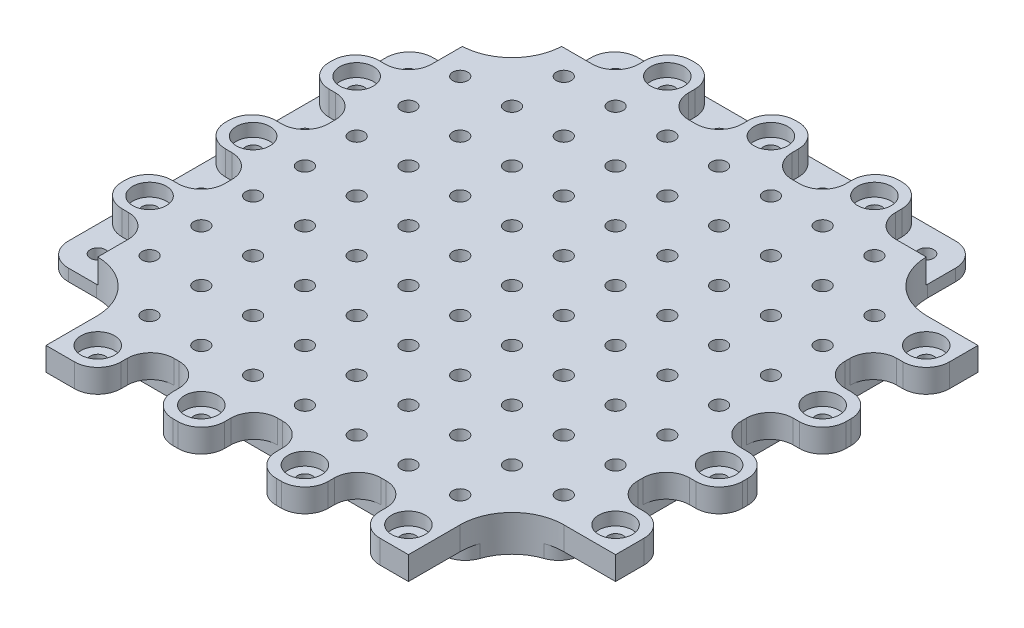
SolidWorks part; units mm, degrees
ref_plane "Alzado" through (0, 0, 0) normal (0, 0, 1) x (1, 0, 0)
ref_plane "Planta" through (0, 0, 0) normal (0, 1, 0) x (1, 0, 0)
ref_plane "Vista lateral" through (0, 0, 0) normal (1, 0, 0) x (0, 0, -1)
sketch "Croquis1" plane through (0, 0, 0) normal (0, 1, 0) x (1, 0, 0)
  line L1 (-50, -50) -> (50, -50)
  line L2 (-50, -50) -> (-50, 50)
  line L3 (-50, 50) -> (50, 50)
  line L4 (50, -50) -> (50, 50)
  line L5 (-50, -50) -> (50, 50) construction
  line L6 (-50, 50) -> (50, -50) construction
  point P0 (0, 0)
  dimension "D1" = 100
  dimension "D2" = 100
extrude "Saliente-Extruir1" add sketch "Croquis1" along normal blind 7
sketch "Croquis2" plane through (0, 7, 0) normal (0, 1, 0) x (1, 0, 0)
  line L45 (-50, 50) -> (-50, -50) construction
  line L50 (-50.2, 50.2) -> (-39.8, 50.2)
  line L55 (-50.2, 50.2) -> (-50.2, 39.8)
  line L60 (-50.2, 39.8) -> (-39.8, 39.8)
  line L65 (-39.8, 50.2) -> (-39.8, 39.8)
  line L70 (50, 50) -> (-50, 50) construction
  line L75 (-30.2, 50.2) -> (-19.8, 50.2)
  line L80 (-30.2, 50.2) -> (-30.2, 39.8)
  line L85 (-30.2, 39.8) -> (-19.8, 39.8)
  line L95 (-19.8, 50.2) -> (-19.8, 39.8)
  line L96 (-10.2, 50.2) -> (0.2, 50.2)
  line L97 (-10.2, 50.2) -> (-10.2, 39.8)
  line L98 (-10.2, 39.8) -> (0.2, 39.8)
  line L99 (0.2, 50.2) -> (0.2, 39.8)
  line L100 (9.8, 50.2) -> (20.2, 50.2)
  line L101 (9.8, 50.2) -> (9.8, 39.8)
  line L102 (9.8, 39.8) -> (20.2, 39.8)
  line L103 (20.2, 50.2) -> (20.2, 39.8)
  line L104 (29.8, 50.2) -> (40.2, 50.2)
  line L105 (29.8, 50.2) -> (29.8, 39.8)
  line L106 (29.8, 39.8) -> (40.2, 39.8)
  line L107 (40.2, 50.2) -> (40.2, 39.8)
  line L108 (-50.2, 30.2) -> (-39.8, 30.2)
  line L109 (-50.2, 30.2) -> (-50.2, 19.8)
  line L110 (-50.2, 19.8) -> (-39.8, 19.8)
  line L111 (-39.8, 30.2) -> (-39.8, 19.8)
  line L112 (-50.2, 10.2) -> (-39.8, 10.2)
  line L113 (-50.2, 10.2) -> (-50.2, -0.2)
  line L114 (-50.2, -0.2) -> (-39.8, -0.2)
  line L115 (-39.8, 10.2) -> (-39.8, -0.2)
  line L116 (-50.2, -9.8) -> (-39.8, -9.8)
  line L117 (-50.2, -9.8) -> (-50.2, -20.2)
  line L118 (-50.2, -20.2) -> (-39.8, -20.2)
  line L119 (-39.8, -9.8) -> (-39.8, -20.2)
  line L120 (-50.2, -29.8) -> (-39.8, -29.8)
  line L121 (-50.2, -29.8) -> (-50.2, -40.2)
  line L122 (-50.2, -40.2) -> (-39.8, -40.2)
  line L123 (-39.8, -29.8) -> (-39.8, -40.2)
  dimension "D3" = 0.2
  dimension "D1" = 10.4
  dimension "D2" = 10.4
  dimension "D4" = 0.2
  dimension "D5" = 5
extrude "Cortar-Extruir1" cut sketch "Croquis2" against normal blind 4.7
sketch "Croquis3" plane through (0, 7, 0) normal (0, 1, 0) x (1, 0, 0)
  line L0 (50, 30) -> (60, 30)
  line L5 (50, 50) -> (60, 50)
  line L6 (50, 50) -> (50, 40)
  line L7 (50, 40) -> (60, 40)
  line L8 (60, 50) -> (60, 40)
  line L9 (50, 30) -> (50, 20)
  line L10 (50, 20) -> (60, 20)
  line L11 (60, 30) -> (60, 20)
  line L12 (50, 10) -> (60, 10)
  line L13 (50, 10) -> (50, 0)
  line L14 (50, 0) -> (60, 0)
  line L15 (60, 10) -> (60, 0)
  line L16 (50, -10) -> (60, -10)
  line L17 (50, -10) -> (50, -20)
  line L18 (50, -20) -> (60, -20)
  line L19 (60, -10) -> (60, -20)
  line L20 (50, -30) -> (60, -30)
  line L21 (50, -30) -> (50, -40)
  line L22 (50, -40) -> (60, -40)
  line L23 (60, -30) -> (60, -40)
  line L24 (-30, -50) -> (-20, -50)
  line L25 (-50, -50) -> (-40, -50)
  line L26 (-50, -50) -> (-50, -60)
  line L27 (-50, -60) -> (-40, -60)
  line L28 (-40, -50) -> (-40, -60)
  line L29 (-30, -50) -> (-30, -60)
  line L30 (-30, -60) -> (-20, -60)
  line L31 (-20, -50) -> (-20, -60)
  line L32 (-10, -50) -> (0, -50)
  line L33 (-10, -50) -> (-10, -60)
  line L34 (-10, -60) -> (0, -60)
  line L35 (0, -50) -> (0, -60)
  line L36 (10, -50) -> (20, -50)
  line L37 (10, -50) -> (10, -60)
  line L38 (10, -60) -> (20, -60)
  line L39 (20, -50) -> (20, -60)
  line L40 (30, -50) -> (40, -50)
  line L41 (30, -50) -> (30, -60)
  line L42 (30, -60) -> (40, -60)
  line L43 (40, -50) -> (40, -60)
  dimension "D1" = 10
  dimension "D2" = 10
  dimension "D4" = 10
  dimension "D5" = 10
  dimension "D3" = 5
extrude "Saliente-Extruir2" add sketch "Croquis3" against normal blind 4.5
sketch "Croquis4" plane through (0, 7, 0) normal (0, 1, 0) x (1, 0, 0)
  line L0 (60, 45) -> (-63.1643, 45) construction
  line L1 (60, 40) -> (60, 50) construction
  line L2 (-45, -60) -> (-45, 61.9533) construction
  line L3 (-50, -60) -> (-40, -60) construction
  circle A0 centre (-45, 45) radius 1.45
  circle A1 centre (-35, 45) radius 1.45
  circle A2 centre (-25, 45) radius 1.45
  circle A3 centre (-15, 45) radius 1.45
  circle A4 centre (-5, 45) radius 1.45
  circle A5 centre (5, 45) radius 1.45
  circle A6 centre (15, 45) radius 1.45
  circle A7 centre (25, 45) radius 1.45
  circle A8 centre (35, 45) radius 1.45
  circle A9 centre (45, 45) radius 1.45
  circle A10 centre (55, 45) radius 1.45
  circle A11 centre (-35, 35) radius 1.45
  circle A12 centre (-25, 35) radius 1.45
  circle A13 centre (-15, 35) radius 1.45
  circle A14 centre (-5, 35) radius 1.45
  circle A15 centre (5, 35) radius 1.45
  circle A16 centre (15, 35) radius 1.45
  circle A17 centre (25, 35) radius 1.45
  circle A18 centre (35, 35) radius 1.45
  circle A19 centre (45, 35) radius 1.45
  circle A20 centre (55, 35) radius 1.45
  circle A21 centre (-35, 25) radius 1.45
  circle A22 centre (-25, 25) radius 1.45
  circle A23 centre (-15, 25) radius 1.45
  circle A24 centre (-5, 25) radius 1.45
  circle A25 centre (5, 25) radius 1.45
  circle A26 centre (15, 25) radius 1.45
  circle A27 centre (25, 25) radius 1.45
  circle A28 centre (35, 25) radius 1.45
  circle A29 centre (45, 25) radius 1.45
  circle A30 centre (55, 25) radius 1.45
  circle A31 centre (-35, 15) radius 1.45
  circle A32 centre (-25, 15) radius 1.45
  circle A33 centre (-15, 15) radius 1.45
  circle A34 centre (-5, 15) radius 1.45
  circle A35 centre (5, 15) radius 1.45
  circle A36 centre (15, 15) radius 1.45
  circle A37 centre (25, 15) radius 1.45
  circle A38 centre (35, 15) radius 1.45
  circle A39 centre (45, 15) radius 1.45
  circle A40 centre (55, 15) radius 1.45
  circle A41 centre (-35, 5) radius 1.45
  circle A42 centre (-25, 5) radius 1.45
  circle A43 centre (-15, 5) radius 1.45
  circle A44 centre (-5, 5) radius 1.45
  circle A45 centre (5, 5) radius 1.45
  circle A46 centre (15, 5) radius 1.45
  circle A47 centre (25, 5) radius 1.45
  circle A48 centre (35, 5) radius 1.45
  circle A49 centre (45, 5) radius 1.45
  circle A50 centre (55, 5) radius 1.45
  circle A51 centre (-35, -5) radius 1.45
  circle A52 centre (-25, -5) radius 1.45
  circle A53 centre (-15, -5) radius 1.45
  circle A54 centre (-5, -5) radius 1.45
  circle A55 centre (5, -5) radius 1.45
  circle A56 centre (15, -5) radius 1.45
  circle A57 centre (25, -5) radius 1.45
  circle A58 centre (35, -5) radius 1.45
  circle A59 centre (45, -5) radius 1.45
  circle A60 centre (55, -5) radius 1.45
  circle A61 centre (-35, -15) radius 1.45
  circle A62 centre (-25, -15) radius 1.45
  circle A63 centre (-15, -15) radius 1.45
  circle A64 centre (-5, -15) radius 1.45
  circle A65 centre (5, -15) radius 1.45
  circle A66 centre (15, -15) radius 1.45
  circle A67 centre (25, -15) radius 1.45
  circle A68 centre (35, -15) radius 1.45
  circle A69 centre (45, -15) radius 1.45
  circle A70 centre (55, -15) radius 1.45
  circle A71 centre (-35, -25) radius 1.45
  circle A72 centre (-25, -25) radius 1.45
  circle A73 centre (-15, -25) radius 1.45
  circle A74 centre (-5, -25) radius 1.45
  circle A75 centre (5, -25) radius 1.45
  circle A76 centre (15, -25) radius 1.45
  circle A77 centre (25, -25) radius 1.45
  circle A78 centre (35, -25) radius 1.45
  circle A79 centre (45, -25) radius 1.45
  circle A80 centre (55, -25) radius 1.45
  circle A81 centre (-35, -35) radius 1.45
  circle A82 centre (-25, -35) radius 1.45
  circle A83 centre (-15, -35) radius 1.45
  circle A84 centre (-5, -35) radius 1.45
  circle A85 centre (5, -35) radius 1.45
  circle A86 centre (15, -35) radius 1.45
  circle A87 centre (25, -35) radius 1.45
  circle A88 centre (35, -35) radius 1.45
  circle A89 centre (45, -35) radius 1.45
  circle A90 centre (55, -35) radius 1.45
  circle A91 centre (-35, -45) radius 1.45
  circle A92 centre (-25, -45) radius 1.45
  circle A93 centre (-15, -45) radius 1.45
  circle A94 centre (-5, -45) radius 1.45
  circle A95 centre (5, -45) radius 1.45
  circle A96 centre (15, -45) radius 1.45
  circle A97 centre (25, -45) radius 1.45
  circle A98 centre (35, -45) radius 1.45
  circle A99 centre (45, -45) radius 1.45
  circle A100 centre (55, -45) radius 1.45
  circle A101 centre (-35, -55) radius 1.45
  circle A102 centre (-25, -55) radius 1.45
  circle A103 centre (-15, -55) radius 1.45
  circle A104 centre (-5, -55) radius 1.45
  circle A105 centre (5, -55) radius 1.45
  circle A106 centre (15, -55) radius 1.45
  circle A107 centre (25, -55) radius 1.45
  circle A108 centre (35, -55) radius 1.45
  circle A109 centre (45, -55) radius 1.45
  circle A110 centre (55, -55) radius 1.45
  circle A111 centre (-45, 35) radius 1.45
  circle A112 centre (-45, 25) radius 1.45
  circle A113 centre (-45, 15) radius 1.45
  circle A114 centre (-45, 5) radius 1.45
  circle A115 centre (-45, -5) radius 1.45
  circle A116 centre (-45, -15) radius 1.45
  circle A117 centre (-45, -25) radius 1.45
  circle A118 centre (-45, -35) radius 1.45
  circle A119 centre (-45, -45) radius 1.45
  circle A120 centre (-45, -55) radius 1.45
  dimension "D1" = 2.9
  dimension "D2" = 11
extrude "Cortar-Extruir2" cut sketch "Croquis4" against normal blind 7
sketch "Croquis5" plane through (0, 7, 0) normal (0, 1, 0) x (1, 0, 0)
  circle A0 centre (-45, 45) radius 3.25
  circle A1 centre (-35, 45) radius 3.25
  circle A2 centre (-25, 45) radius 3.25
  circle A3 centre (-15, 45) radius 3.25
  circle A4 centre (-5, 45) radius 3.25
  circle A5 centre (5, 45) radius 3.25
  circle A6 centre (15, 45) radius 3.25
  circle A7 centre (25, 45) radius 3.25
  circle A8 centre (35, 45) radius 3.25
  circle A9 centre (45, 45) radius 3.25
  circle A10 centre (55, 45) radius 3.25
  circle A20 centre (55, 35) radius 3.25
  circle A30 centre (55, 25) radius 3.25
  circle A40 centre (55, 15) radius 3.25
  circle A50 centre (55, 5) radius 3.25
  circle A60 centre (55, -5) radius 3.25
  circle A70 centre (55, -15) radius 3.25
  circle A80 centre (55, -25) radius 3.25
  circle A90 centre (55, -35) radius 3.25
  circle A100 centre (55, -45) radius 3.25
  circle A101 centre (-35, -55) radius 3.25
  circle A102 centre (-25, -55) radius 3.25
  circle A103 centre (-15, -55) radius 3.25
  circle A104 centre (-5, -55) radius 3.25
  circle A105 centre (5, -55) radius 3.25
  circle A106 centre (15, -55) radius 3.25
  circle A107 centre (25, -55) radius 3.25
  circle A108 centre (35, -55) radius 3.25
  circle A109 centre (45, -55) radius 3.25
  circle A110 centre (55, -55) radius 3.25
  circle A111 centre (-45, 35) radius 3.25
  circle A112 centre (-45, 25) radius 3.25
  circle A113 centre (-45, 15) radius 3.25
  circle A114 centre (-45, 5) radius 3.25
  circle A115 centre (-45, -5) radius 3.25
  circle A116 centre (-45, -15) radius 3.25
  circle A117 centre (-45, -25) radius 3.25
  circle A118 centre (-45, -35) radius 3.25
  circle A119 centre (-45, -45) radius 3.25
  circle A120 centre (-45, -55) radius 3.25
  circle A121 centre (-35, 35) radius 3.25 [skipped]
  circle A122 centre (-25, 35) radius 3.25 [skipped]
  circle A123 centre (-15, 35) radius 3.25 [skipped]
  circle A124 centre (-5, 35) radius 3.25 [skipped]
  circle A125 centre (5, 35) radius 3.25 [skipped]
  circle A126 centre (15, 35) radius 3.25 [skipped]
  circle A127 centre (25, 35) radius 3.25 [skipped]
  circle A128 centre (35, 35) radius 3.25 [skipped]
  circle A129 centre (45, 35) radius 3.25 [skipped]
  circle A130 centre (-35, 25) radius 3.25 [skipped]
  circle A131 centre (-25, 25) radius 3.25 [skipped]
  circle A132 centre (-15, 25) radius 3.25 [skipped]
  circle A133 centre (-5, 25) radius 3.25 [skipped]
  circle A134 centre (5, 25) radius 3.25 [skipped]
  circle A135 centre (15, 25) radius 3.25 [skipped]
  circle A136 centre (25, 25) radius 3.25 [skipped]
  circle A137 centre (35, 25) radius 3.25 [skipped]
  circle A138 centre (45, 25) radius 3.25 [skipped]
  circle A139 centre (-35, 15) radius 3.25 [skipped]
  circle A140 centre (-25, 15) radius 3.25 [skipped]
  circle A141 centre (-15, 15) radius 3.25 [skipped]
  circle A142 centre (-5, 15) radius 3.25 [skipped]
  circle A143 centre (5, 15) radius 3.25 [skipped]
  circle A144 centre (15, 15) radius 3.25 [skipped]
  circle A145 centre (25, 15) radius 3.25 [skipped]
  circle A146 centre (35, 15) radius 3.25 [skipped]
  circle A147 centre (45, 15) radius 3.25 [skipped]
  circle A148 centre (-35, 5) radius 3.25 [skipped]
  circle A149 centre (-25, 5) radius 3.25 [skipped]
  circle A150 centre (-15, 5) radius 3.25 [skipped]
  circle A151 centre (-5, 5) radius 3.25 [skipped]
  circle A152 centre (5, 5) radius 3.25 [skipped]
  circle A153 centre (15, 5) radius 3.25 [skipped]
  circle A154 centre (25, 5) radius 3.25 [skipped]
  circle A155 centre (35, 5) radius 3.25 [skipped]
  circle A156 centre (45, 5) radius 3.25 [skipped]
  circle A157 centre (-35, -5) radius 3.25 [skipped]
  circle A158 centre (-25, -5) radius 3.25 [skipped]
  circle A159 centre (-15, -5) radius 3.25 [skipped]
  circle A160 centre (-5, -5) radius 3.25 [skipped]
  circle A161 centre (5, -5) radius 3.25 [skipped]
  circle A162 centre (15, -5) radius 3.25 [skipped]
  circle A163 centre (25, -5) radius 3.25 [skipped]
  circle A164 centre (35, -5) radius 3.25 [skipped]
  circle A165 centre (45, -5) radius 3.25 [skipped]
  circle A166 centre (-35, -15) radius 3.25 [skipped]
  circle A167 centre (-25, -15) radius 3.25 [skipped]
  circle A168 centre (-15, -15) radius 3.25 [skipped]
  circle A169 centre (-5, -15) radius 3.25 [skipped]
  circle A170 centre (5, -15) radius 3.25 [skipped]
  circle A171 centre (15, -15) radius 3.25 [skipped]
  circle A172 centre (25, -15) radius 3.25 [skipped]
  circle A173 centre (35, -15) radius 3.25 [skipped]
  circle A174 centre (45, -15) radius 3.25 [skipped]
  circle A175 centre (-35, -25) radius 3.25 [skipped]
  circle A176 centre (-25, -25) radius 3.25 [skipped]
  circle A177 centre (-15, -25) radius 3.25 [skipped]
  circle A178 centre (-5, -25) radius 3.25 [skipped]
  circle A179 centre (5, -25) radius 3.25 [skipped]
  circle A180 centre (15, -25) radius 3.25 [skipped]
  circle A181 centre (25, -25) radius 3.25 [skipped]
  circle A182 centre (35, -25) radius 3.25 [skipped]
  circle A183 centre (45, -25) radius 3.25 [skipped]
  circle A184 centre (-35, -35) radius 3.25 [skipped]
  circle A185 centre (-25, -35) radius 3.25 [skipped]
  circle A186 centre (-15, -35) radius 3.25 [skipped]
  circle A187 centre (-5, -35) radius 3.25 [skipped]
  circle A188 centre (5, -35) radius 3.25 [skipped]
  circle A189 centre (15, -35) radius 3.25 [skipped]
  circle A190 centre (25, -35) radius 3.25 [skipped]
  circle A191 centre (35, -35) radius 3.25 [skipped]
  circle A192 centre (45, -35) radius 3.25 [skipped]
  circle A193 centre (-35, -45) radius 3.25 [skipped]
  circle A194 centre (-25, -45) radius 3.25 [skipped]
  circle A195 centre (-15, -45) radius 3.25 [skipped]
  circle A196 centre (-5, -45) radius 3.25 [skipped]
  circle A197 centre (5, -45) radius 3.25 [skipped]
  circle A198 centre (15, -45) radius 3.25 [skipped]
  circle A199 centre (25, -45) radius 3.25 [skipped]
  circle A200 centre (35, -45) radius 3.25 [skipped]
  circle A201 centre (45, -45) radius 3.25 [skipped]
  dimension "D1" = 6.5
  dimension "D3" = 11
  dimension "D2" = 11
extrude "Cortar-Extruir4" cut sketch "Croquis5" against normal blind 2.5
sketch "Croquis6" plane through (0, 7, 0) normal (0, 1, 0) x (1, 0, 0)
  line L0 (50, -50) -> (40, -50)
  line L1 (50, -50) -> (50, -49.8)
  line L2 (40, -50) -> (40, -49.8)
  line L3 (49.8, -49.8) -> (40, -49.8)
  line L4 (30, -50) -> (20, -50)
  line L5 (30, -50) -> (30, -49.8)
  line L6 (20, -50) -> (20, -49.8)
  line L7 (30, -49.8) -> (20, -49.8)
  line L8 (10, -50) -> (0, -50)
  line L9 (10, -50) -> (10, -49.8)
  line L10 (0, -50) -> (0, -49.8)
  line L11 (10, -49.8) -> (0, -49.8)
  line L12 (-10, -50) -> (-20, -50)
  line L13 (-10, -50) -> (-10, -49.8)
  line L14 (-20, -50) -> (-20, -49.8)
  line L15 (-10, -49.8) -> (-20, -49.8)
  line L16 (-30, -50) -> (-40, -50)
  line L17 (-30, -50) -> (-30, -49.8)
  line L18 (-40, -50) -> (-40, -49.8)
  line L19 (-30, -49.8) -> (-40, -49.8)
  line L20 (50, -49.8) -> (50, -40)
  line L22 (50, -40) -> (49.8, -40)
  line L23 (49.8, -49.8) -> (49.8, -40)
  line L24 (50, -29.8) -> (50, -20)
  line L25 (50, -29.8) -> (49.8, -29.8)
  line L26 (50, -20) -> (49.8, -20)
  line L27 (49.8, -29.8) -> (49.8, -20)
  line L28 (50, -9.8) -> (50, 0)
  line L29 (50, -9.8) -> (49.8, -9.8)
  line L30 (50, 0) -> (49.8, 0)
  line L31 (49.8, -9.8) -> (49.8, 0)
  line L32 (50, 10.2) -> (50, 20)
  line L33 (50, 10.2) -> (49.8, 10.2)
  line L34 (50, 20) -> (49.8, 20)
  line L35 (49.8, 10.2) -> (49.8, 20)
  line L36 (50, 30.2) -> (50, 40)
  line L37 (50, 30.2) -> (49.8, 30.2)
  line L38 (50, 40) -> (49.8, 40)
  line L39 (49.8, 30.2) -> (49.8, 40)
  dimension "D1" = 0.2
  dimension "D2" = 0.2
  dimension "D3" = 5
extrude "Cortar-Extruir5" cut sketch "Croquis6" against normal blind 7
sketch "Croquis8" plane through (0, 7, 0) normal (0, 1, 0) x (1, 0, 0)
  line L1 (49.8, 40) -> (60, 40)
  line L2 (49.8, 40) -> (49.8, 50)
  line L3 (49.8, 50) -> (60, 50)
  line L4 (60, 40) -> (60, 50)
extrude "Cortar-Extruir7" cut sketch "Croquis8" against normal blind 7
sketch "Croquis9" plane through (0, 0, 0) normal (0, -1, 0) x (1, 0, 0)
  line L0 (-40, 50) -> (-40, 49.8)
  line L1 (-40, 50) -> (-50.0122, 50)
  line L2 (-40, 49.8) -> (-50.0122, 49.8)
  line L3 (-50.0122, 50) -> (-50.0122, 49.8)
  line L4 (-20, 50) -> (-20, 49.8)
  line L5 (-20, 50) -> (-30.0122, 50)
  line L6 (-20, 49.8) -> (-30.0122, 49.8)
  line L7 (-30.0122, 50) -> (-30.0122, 49.8)
  line L8 (0, 50) -> (0, 49.8)
  line L9 (0, 50) -> (-10.0122, 50)
  line L10 (0, 49.8) -> (-10.0122, 49.8)
  line L11 (-10.0122, 50) -> (-10.0122, 49.8)
  line L12 (20, 50) -> (20, 49.8)
  line L13 (20, 50) -> (9.9878, 50)
  line L14 (20, 49.8) -> (9.9878, 49.8)
  line L15 (9.9878, 50) -> (9.9878, 49.8)
  line L16 (40, 50) -> (40, 49.8)
  line L17 (40, 50) -> (29.9878, 50)
  line L18 (40, 49.8) -> (29.9878, 49.8)
  line L19 (29.9878, 50) -> (29.9878, 49.8)
  line L20 (50, -20) -> (50, -30.2)
  line L21 (50, -20) -> (49.8, -20)
  line L22 (50, -30.2) -> (49.8, -30.2)
  line L23 (49.8, -20) -> (49.8, -30.2)
  line L24 (49.8, -50) -> (49.8, -30.2) construction
  line L25 (50, 0) -> (50, -10.2)
  line L26 (50, 0) -> (49.8, 0)
  line L27 (50, -10.2) -> (49.8, -10.2)
  line L28 (49.8, 0) -> (49.8, -10.2)
  line L29 (50, 20) -> (50, 9.8)
  line L30 (50, 20) -> (49.8, 20)
  line L31 (50, 9.8) -> (49.8, 9.8)
  line L32 (49.8, 20) -> (49.8, 9.8)
  line L33 (50, 40) -> (50, 29.8)
  line L34 (50, 40) -> (49.8, 40)
  line L35 (50, 29.8) -> (49.8, 29.8)
  line L36 (49.8, 40) -> (49.8, 29.8)
  dimension "D1" = 0
  dimension "D2" = 4
extrude "Cortar-Extruir9" cut sketch "Croquis9" against normal blind 2.5
sketch "Croquis10" plane through (0, 2.5, 0) normal (0, -1, 0) x (1, 0, 0)
  line L0 (50, 30) -> (50, 29.8)
  line L1 (50, 30) -> (49.8, 30)
  line L2 (50, 29.8) -> (49.8, 29.8)
  line L3 (49.8, 30) -> (49.8, 29.8)
  line L4 (50, 10) -> (50, 9.8)
  line L5 (50, 10) -> (49.8, 10)
  line L6 (49.8, 10) -> (49.8, 9.8)
  line L7 (50, 9.8) -> (49.8, 9.8)
  line L8 (50, -10) -> (50, -10.2)
  line L9 (50, -10) -> (49.8, -10)
  line L10 (49.8, -10) -> (49.8, -10.2)
  line L11 (50, -10.2) -> (49.8, -10.2)
  line L12 (50, -30) -> (50, -30.2)
  line L13 (50, -30) -> (49.8, -30)
  line L14 (49.8, -30) -> (49.8, -30.2)
  line L15 (50, -30.2) -> (49.8, -30.2)
  line L16 (49.8, -20) -> (49.8, -30.2) construction
  dimension "D2" = 0
  dimension "D1" = 4
extrude "Cortar-Extruir11" cut sketch "Croquis10" against normal blind 5
sketch "Croquis11" plane through (0, 7, 0) normal (0, 1, 0) x (1, 0, 0)
  line L1 (-50, -60) -> (-40, -60)
  line L2 (-50, -60) -> (-50, -49.8)
  line L3 (-50, -49.8) -> (-40, -49.8)
  line L4 (-40, -60) -> (-40, -49.8)
  line L5 (-50, 50) -> (-39.8, 50)
  line L6 (-50, 50) -> (-50, 39.8)
  line L7 (-50, 39.8) -> (-39.8, 39.8)
  line L8 (-39.8, 50) -> (-39.8, 39.8)
extrude "Cortar-Extruir12" cut sketch "Croquis11" against normal blind 10
sketch "Croquis12" plane through (0, 7, 0) normal (0, 1, 0) x (1, 0, 0)
  line L0 (0, 0) -> (0, 59.9153) construction
  line L1 (-50, 30.2) -> (-30.2, 30.2)
  line L2 (-50, 30.2) -> (-50, 50)
  line L3 (-50, 50) -> (-30.2, 50)
  line L4 (-30.2, 30.2) -> (-30.2, 50)
  line L5 (0, 0) -> (80.9793, 0) construction
  line L6 (60, 30) -> (49.8, 30) construction
  line L7 (40.2, 50) -> (49.8, 50)
  line L8 (40.2, 50) -> (40.2, 30)
  line L9 (40.2, 30) -> (49.8, 30)
  line L10 (49.8, 50) -> (49.8, 30)
  line L11 (49.8, 50) -> (49.8, 30) construction
  line L12 (40, -60) -> (40, -49.8) construction
  line L13 (40, -60) -> (49.8, -60)
  line L14 (40, -60) -> (40, -40)
  line L15 (40, -40) -> (49.8, -40)
  line L16 (49.8, -60) -> (49.8, -40)
  line L17 (-50, -40.2) -> (-30, -40.2)
  line L18 (-50, -40.2) -> (-50, -49.8)
  line L19 (-50, -49.8) -> (-30, -49.8)
  line L20 (-30, -40.2) -> (-30, -49.8)
  line L21 (40.2, 39.8) -> (40.2, 50) construction
  line L22 (49.8, 50) -> (40.2, 50) construction
  point P35 (40.2, 44.9)
  dimension "D1" = 0
  dimension "D2" = 0
  dimension "D3" = 0
extrude "Cortar-Extruir13" cut sketch "Croquis12" against normal blind 10
fillet "Redondeo1" radius 10 4 edges at (-30, 3.5, 40.2) (40, 3.5, 40) (-30.2, 3.5, -30.2) (40.2, 3.5, -30)
fillet "Redondeo2" radius 4.5 48 edges at (9.8, 4.65, -39.8) (29.8, 4.65, -39.8) (0.2, 4.65, -39.8) (9.8, 4.65, -50) (0.2, 4.65, -50) (20.2, 4.65, -39.8) (29.8, 4.65, -50) (20.2, 4.65, -50) (-10.2, 4.65, -39.8) (-10.2, 4.65, -50) (-19.8, 4.65, -50) (-19.8, 4.65, -39.8) (-39.8, 4.65, 9.8) (-39.8, 4.65, -10.2) (-39.8, 4.65, -19.8) (-50, 4.65, -19.8) (-50, 4.65, -10.2) (-39.8, 4.65, 0.2) (-50, 4.65, 0.2) (-50, 4.65, 9.8) (-50, 4.65, 20.2) (-39.8, 4.65, 20.2) (-50, 4.65, 29.8) (-39.8, 4.65, 29.8) (-20, 4.75, 60) (-20, 4.75, 49.8) (-10, 4.75, 60) (-10, 4.75, 49.8) (0, 4.75, 60) (0, 4.75, 49.8) (10, 4.75, 49.8) (10, 4.75, 60) (20, 4.75, 60) (20, 4.75, 49.8) (30, 4.75, 60) (30, 4.75, 49.8) (60, 4.75, -20) (49.8, 4.75, -20) (49.8, 4.75, -10) (60, 4.75, -10) (49.8, 4.75, 10) (60, 4.75, 0) (49.8, 4.75, 0) (60, 4.75, 10) (60, 4.75, 20) (49.8, 4.75, 20) (60, 4.75, 30) (49.8, 4.75, 30)
fillet "Redondeo3" radius 4.5 8 edges at (-30.008, 1.25, 49.8) (40.002, 1.25, 49.8) (49.8, 1.25, 40.002) (49.8, 1.25, -30.008) (-50, 1.15, 40.2) (-50, 1.15, -30.2) (-30.2, 1.15, -50) (40.2, 1.15, -50)
